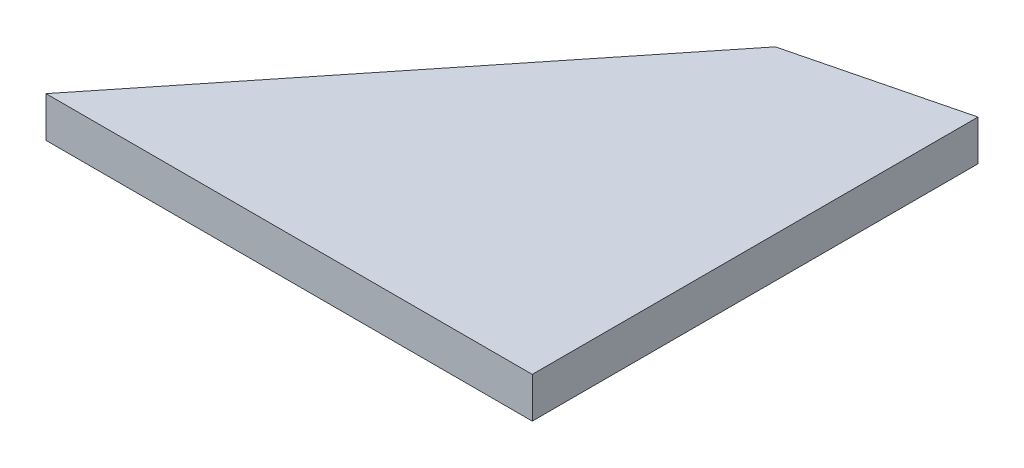
SolidWorks part; units mm, degrees
ref_plane "Front Plane" through (0, 0, 0) normal (0, 0, 1) x (1, 0, 0)
ref_plane "Top Plane" through (0, 0, 0) normal (0, 1, 0) x (1, 0, 0)
ref_plane "Right Plane" through (0, 0, 0) normal (1, 0, 0) x (0, 0, -1)
sketch "Sketch1" plane through (0, 0, 0) normal (0, 1, 0) x (1, 0, 0)
  line L0 (0, 0) -> (40, 50)
  line L1 (40, 50) -> (60, 55)
  line L2 (60, 55) -> (60, 0)
  line L3 (60, 0) -> (0, 0)
  dimension "D1" = 60
  dimension "D2" = 55
  dimension "D3" = 40
  dimension "D4" = 50
extrude "Boss-Extrude1" add sketch "Sketch1" along normal mid plane 5
